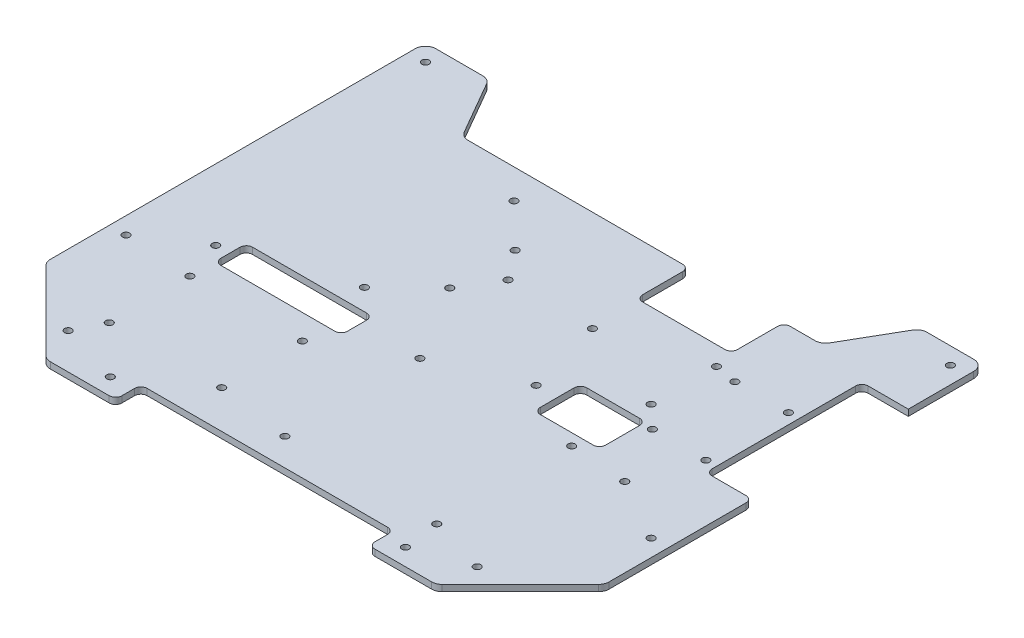
SolidWorks part; units mm, degrees
material "Acier non allié"
ref_plane "Front" through (0, 0, 0) normal (0, 0, 1) x (1, 0, 0)
ref_plane "Top" through (0, 0, 0) normal (0, 1, 0) x (1, 0, 0)
ref_plane "Right" through (0, 0, 0) normal (1, 0, 0) x (0, 0, -1)
sketch "Esquisse1" plane through (0, 0, 0) normal (0, 1, 0) x (1, 0, 0)
  line L0 (0, 0) -> (0, 190) construction
  line L1 (-92.5, 0) -> (92.5, 0)
  line L2 (92.5, 0) -> (132.5, 40)
  line L3 (132.5, 40) -> (132.5, 220)
  line L4 (132.5, 220) -> (102.5, 220)
  line L5 (102.5, 220) -> (85.1795, 190)
  line L6 (85.1795, 190) -> (-85.1795, 190)
  line L7 (-102.5, 220) -> (-85.1795, 190)
  line L8 (-132.5, 220) -> (-102.5, 220)
  line L9 (-132.5, 40) -> (-132.5, 220)
  line L10 (-92.5, 0) -> (-132.5, 40)
  dimension "D1" = 132.5
  dimension "D2" = 220
  dimension "D3" = 60
  dimension "D4" = 30
  dimension "D5" = 40
  dimension "D6" = 40
  dimension "D7" = 30
extrude "Boss.-Extru.1" add sketch "Esquisse1" along normal blind 3
fillet "Congé1" radius 5 10 edges at (92.5, 1.5, 0) (132.5, 1.5, -40) (132.5, 1.5, -220) (102.5, 1.5, -220) (85.1795, 1.5, -190) (-85.1795, 1.5, -190) (-102.5, 1.5, -220) (-132.5, 1.5, -220) (-92.5, 1.5, 0) (-132.5, 1.5, -40)
sketch "Esquisse2" plane through (0, 3, 0) normal (0, 1, 0) x (1, 0, 0)
  line L0 (0, 0) -> (0, 294.1173) construction
  line L2 (-90.4289, 0) -> (90.4289, 0) construction
  circle A0 centre (70, 8) radius 1
  circle A1 centre (124.5, 70) radius 1
  circle A2 centre (124.5, 212) radius 1
  circle A3 centre (-124.5, 212) radius 1
  circle A4 centre (-124.5, 70) radius 1
  circle A5 centre (-70, 8) radius 1
  dimension "D2" = 2
  dimension "D6" = 2
  dimension "D9" = 2
  dimension "D1" = 70
  dimension "D3" = 8
  dimension "D4" = 124.5
  dimension "D5" = 70
  dimension "D7" = 124.5
  dimension "D8" = 212
extrude "Enlèv. mat.-Extru.1" cut sketch "Esquisse2" against normal blind 3
hole_wizard "Dégagement M31" positions "Esquisse3" profile "Esquisse4" hole size "M3" standard "ISO" end condition through all
sketch "Esquisse3" plane through (0, 3, 0) normal (0, 1, 0) x (1, 0, 0)
  point P0 (70, 8)
  point P3 (-70, 8)
  point P6 (-124.5, 70)
  point P9 (-124.5, 212)
  point P12 (124.5, 212)
  point P15 (124.5, 70)
sketch "Esquisse4" plane through (70, 3, -8) normal (1, 0, 0) x (0, 0, 1)
  line L0 (0, 0) -> (0, 3)
  line L1 (0, 3) -> (1.7, 3)
  line L2 (1.7, 3) -> (1.7, 0)
  line L5 (1.7, 0) -> (0, 0)
  line L11 (0, -6.35) -> (0, 107.95) construction
  dimension "Diamètre du perçage jusqu'au prochain" = 3.4
  dimension "Profondeur du perçage jusqu'au prochain" = 3
sketch "Esquisse5" plane through (0, 3, 0) normal (0, 1, 0) x (1, 0, 0)
  line L0 (82.2927, 190) -> (-82.2927, 190) construction
  line L1 (67.5, 190) -> (22.5, 190)
  line L2 (67.5, 190) -> (67.5, 165)
  line L3 (67.5, 165) -> (22.5, 165)
  line L4 (22.5, 190) -> (22.5, 165)
  line L5 (132.5, 42.0711) -> (132.5, 215) construction
  line L6 (132.5, 184) -> (110.5, 184)
  line L7 (132.5, 184) -> (132.5, 110)
  line L8 (132.5, 110) -> (110.5, 110)
  line L9 (110.5, 184) -> (110.5, 110)
  line L10 (127.5, 220) -> (105.3868, 220) construction
  dimension "D1" = 25
  dimension "D2" = 65
  dimension "D3" = 110
  dimension "D4" = 36
  dimension "D5" = 110
  dimension "D6" = 22
extrude "Enlèv. mat.-Extru.2" cut sketch "Esquisse5" against normal through all
fillet "Congé2" radius 3 7 edges at (132.5, 1.5, -110) (110.5, 1.5, -110) (110.5, 1.5, -184) (67.5, 1.5, -190) (67.5, 1.5, -165) (22.5, 1.5, -165) (22.5, 1.5, -190)
sketch "Esquisse6" plane through (0, 3, 0) normal (0, 1, 0) x (1, 0, 0)
  line L0 (110.5, 140.5) -> (-167.6757, 140.5) construction
  line L1 (110.5, 181) -> (110.5, 113) construction
  line L2 (-90.4289, 0) -> (90.4289, 0) construction
  line L3 (110.5, 181) -> (110.5, 113) construction
  circle A0 centre (69.5, 156) radius 1
  circle A1 centre (-26, 156) radius 1
  circle A2 centre (-46.5, 176) radius 1
  circle A3 centre (69.5, 125) radius 1
  circle A4 centre (-26, 125) radius 1
  circle A5 centre (-46.5, 105) radius 1
  dimension "D4" = 2
  dimension "D6" = 2
  dimension "D10" = 2
  dimension "D1" = 140.5
  dimension "D2" = 41
  dimension "D3" = 15.5
  dimension "D5" = 136.5
  dimension "D7" = 15.5
  dimension "D8" = 35.5
  dimension "D9" = 157
extrude "Enlèv. mat.-Extru.3" cut sketch "Esquisse6" against normal through all
hole_wizard "Dégagement M32" positions "Esquisse7" profile "Esquisse8" hole size "M3" standard "ISO"
sketch "Esquisse7" plane through (0, 3, 0) normal (0, 1, 0) x (1, 0, 0)
  point P0 (-46.5, 105)
  point P3 (-26, 125)
  point P6 (-26, 156)
  point P9 (-46.5, 176)
  point P12 (69.5, 156)
  point P15 (69.5, 125)
sketch "Esquisse8" plane through (-46.5, 3, -105) normal (1, 0, 0) x (0, 0, 1)
  line L0 (0, 0) -> (0, 11.0215)
  line L1 (0, 11.0215) -> (1.7, 10)
  line L2 (1.7, 10) -> (1.7, 0)
  line L5 (1.7, 0) -> (0, 0)
  line L10 (0, 11.0215) -> (-1.7, 10) construction
  line L11 (0, -6.35) -> (0, 107.95) construction
  dimension "Diamètre du perçage" = 3.4
  dimension "Profondeur du perçage" = 10
  dimension "Angle de pointe" = 118
sketch "Esquisse9" plane through (0, 3, 0) normal (0, 1, 0) x (1, 0, 0)
  line L0 (132.5, 42.0711) -> (132.5, 107) construction
  line L1 (-90.4289, 0) -> (90.4289, 0) construction
  line L2 (-132.5, 215) -> (-132.5, 42.0711) construction
  line L3 (-39.16, 30) -> (-92.5, 30) construction
  line L4 (-39.16, 30) -> (-39.16, 68.24) construction
  line L5 (-39.16, 68.24) -> (-92.5, 68.24) construction
  line L6 (-92.5, 30) -> (-92.5, 68.24) construction
  line L7 (-4.16, 25) -> (-4.16, 89) construction
  line L8 (25.5, 165) -> (64.5, 165) construction
  line L9 (24.5, 142.1606) -> (-15.5, 142.1606) construction
  line L10 (110.5, 181) -> (110.5, 113) construction
  line L11 (113.5, 110) -> (129.5, 110) construction
  circle A0 centre (105.5, 115) radius 1
  circle A3 centre (105.5, 154.12) radius 1
  circle A6 centre (-92.5, 68.24) radius 1
  circle A7 centre (-39.16, 68.24) radius 1
  circle A8 centre (-39.16, 30) radius 1
  circle A9 centre (-92.5, 30) radius 1
  circle A10 centre (-4.16, 89) radius 1
  circle A11 centre (67.84, 89) radius 1
  circle A12 centre (-4.16, 25) radius 1
  circle A13 centre (67.84, 25) radius 1
  circle A14 centre (-15.5, 142.1606) radius 1
  circle A15 centre (24.5, 142.1606) radius 1
  circle A16 centre (34.5, 105.5) radius 1
  circle A17 centre (80.1, 115) radius 1
  circle A18 centre (80.1, 154.12) radius 1
  dimension "D2" = 2
  dimension "D4" = 2
  dimension "D17" = 2
  dimension "D18" = 2
  dimension "D19" = 2
  dimension "D20" = 2
  dimension "D21" = 2
  dimension "D22" = 2
  dimension "D23" = 2
  dimension "D24" = 2
  dimension "D32" = 2
  dimension "D33" = 2
  dimension "D34" = 2
  dimension "D11" = 2
  dimension "D12" = 2
  dimension "D5" = 27
  dimension "25" = 27
  dimension "D10" = 39.12
  dimension "D13" = 38.24
  dimension "D14" = 53.34
  dimension "D15" = 30
  dimension "D16" = 40
  dimension "D25" = 72
  dimension "D26" = 72
  dimension "D27" = 64
  dimension "D28" = 64
  dimension "D29" = 35
  dimension "D30" = 25
  dimension "D31" = 25
  dimension "D36" = 38
  dimension "D37" = 40
  dimension "D39" = 10
  dimension "D7" = 5
  dimension "D8" = 25.4
  dimension "D9" = 25.4
  dimension "D40" = 39.12
  dimension "D35" = 59.5
  dimension "D38" = 76
extrude "Enlèv. mat.-Extru.4" cut sketch "Esquisse9" against normal through all
hole_wizard "Dégagement M33" positions "Esquisse10" profile "Esquisse11" hole size "M3" standard "ISO"
sketch "Esquisse10" plane through (0, 3, 0) normal (0, 1, 0) x (1, 0, 0)
  point P3 (105.5, 115)
  point P9 (105.5, 154.12)
  point P14 (80.1, 154.12)
  point P17 (80.1, 115)
sketch "Esquisse11" plane through (105.5, 3, -115) normal (1, 0, 0) x (0, 0, 1)
  line L0 (0, 0) -> (0, 11.0215)
  line L1 (0, 11.0215) -> (1.7, 10)
  line L2 (1.7, 10) -> (1.7, 0)
  line L5 (1.7, 0) -> (0, 0)
  line L10 (0, 11.0215) -> (-1.7, 10) construction
  line L11 (0, -6.35) -> (0, 107.95) construction
  dimension "Diamètre du perçage" = 3.4
  dimension "Profondeur du perçage" = 10
  dimension "Angle de pointe" = 118
sketch "Esquisse12" plane through (0, 3, 0) normal (0, 1, 0) x (1, 0, 0)
  line L2 (-90.4289, 0) -> (90.4289, 0) construction
  line L3 (95, 17) -> (-99, 17) construction
  line L4 (95, 17) -> (95, 87) construction
  line L5 (95, 87) -> (-99, 87) construction
  line L6 (-99, 17) -> (-99, 87) construction
  line L7 (132.5, 42.0711) -> (132.5, 107) construction
  circle A4 centre (-99, 87) radius 1
  circle A5 centre (95, 87) radius 1
  circle A6 centre (95, 17) radius 1
  circle A7 centre (-99, 17) radius 1
  point P6 (95, 52)
  dimension "D5" = 2
  dimension "D6" = 2
  dimension "D7" = 2
  dimension "D8" = 2
  dimension "D1" = 70
  dimension "D2" = 194
  dimension "D3" = 17
  dimension "D4" = 37.5
extrude "Enlèv. mat.-Extru.5" cut sketch "Esquisse12" against normal through all and the other way through all
hole_wizard "Dégagement M34" positions "Esquisse13" profile "Esquisse14" hole size "M3" standard "ISO"
sketch "Esquisse13" plane through (0, 3, 0) normal (0, 1, 0) x (1, 0, 0)
  point P3 (-92.5, 68.24)
  point P6 (-92.5, 30)
  point P9 (-39.16, 30)
  point P12 (-39.16, 68.24)
  point P16 (-4.16, 25)
  point P19 (67.84, 25)
  point P22 (-4.16, 89)
  point P25 (67.84, 89)
  point P29 (34.5, 105.5)
  point P32 (24.5, 142.1606)
  point P35 (-15.5, 142.1606)
sketch "Esquisse14" plane through (-92.5, 3, -68.24) normal (1, 0, 0) x (0, 0, 1)
  line L0 (0, 0) -> (0, 11.0215)
  line L1 (0, 11.0215) -> (1.7, 10)
  line L2 (1.7, 10) -> (1.7, 0)
  line L5 (1.7, 0) -> (0, 0)
  line L10 (0, 11.0215) -> (-1.7, 10) construction
  line L11 (0, -6.35) -> (0, 107.95) construction
  dimension "Diamètre du perçage" = 3.4
  dimension "Profondeur du perçage" = 10
  dimension "Angle de pointe" = 118
hole_wizard "Dégagement M35" positions "Esquisse15" profile "Esquisse16" hole size "M3" standard "ISO"
sketch "Esquisse15" plane through (0, 3, 0) normal (0, 1, 0) x (1, 0, 0)
  point P0 (-99, 17)
  point P3 (-99, 87)
  point P6 (95, 87)
  point P9 (95, 17)
sketch "Esquisse16" plane through (-99, 3, -17) normal (1, 0, 0) x (0, 0, 1)
  line L0 (0, 0) -> (0, 11.0215)
  line L1 (0, 11.0215) -> (1.7, 10)
  line L2 (1.7, 10) -> (1.7, 0)
  line L5 (1.7, 0) -> (0, 0)
  line L10 (0, 11.0215) -> (-1.7, 10) construction
  line L11 (0, -6.35) -> (0, 107.95) construction
  dimension "Diamètre du perçage" = 3.4
  dimension "Profondeur du perçage" = 10
  dimension "Angle de pointe" = 118
sketch "Esquisse17" plane through (0, 3, 0) normal (0, 1, 0) x (1, 0, 0)
  line L0 (-90.4289, 0) -> (90.4289, 0) construction
  line L1 (-92.5, 95) -> (-32.5, 95)
  line L2 (-92.5, 95) -> (-92.5, 80)
  line L3 (-92.5, 80) -> (-32.5, 80)
  line L4 (-32.5, 95) -> (-32.5, 80)
  line L5 (-132.5, 215) -> (-132.5, 42.0711) construction
  line L6 (132.5, 42.0711) -> (132.5, 107) construction
  line L7 (44.5, 116.5) -> (75.5, 116.5)
  line L8 (44.5, 116.5) -> (44.5, 94.5)
  line L9 (44.5, 94.5) -> (75.5, 94.5)
  line L10 (75.5, 116.5) -> (75.5, 94.5)
  line L11 (82.2927, 190) -> (70.5, 190) construction
  line L13 (-59.5, 12) -> (60.5, 12)
  line L14 (-59.5, 12) -> (-59.5, 0)
  line L15 (-59.5, 0) -> (60.5, 0)
  line L16 (60.5, 12) -> (60.5, 0)
  dimension "D1" = 60
  dimension "D2" = 15
  dimension "D3" = 80
  dimension "D4" = 40
  dimension "D5" = 31
  dimension "D6" = 22
  dimension "D7" = 57
  dimension "D8" = 73.5
  dimension "D9" = 12
  dimension "D11" = 120
  dimension "D12" = 72
extrude "Enlèv. mat.-Extru.6" cut sketch "Esquisse17" against normal up to surface (3 mm away) up to face at (-99, 0, -15.3)
fillet "Congé3" radius 3 12 edges at (60.5, 1.5, 0) (60.5, 1.5, -12) (-59.5, 1.5, -12) (-59.5, 1.5, 0) (44.5, 1.5, -116.5) (75.5, 1.5, -116.5) (75.5, 1.5, -94.5) (44.5, 1.5, -94.5) (-92.5, 1.5, -80) (-32.5, 1.5, -80) (-32.5, 1.5, -95) (-92.5, 1.5, -95)
equation "\"WIDTH\"= 300mm'Total width of the robot"
equation "\"LENGTH\"= 220mm'Total length of the robot"
equation "\"CUT_DEPTH\"= 45mm'Depth of the cut on the edges of the plate"
equation "\"Plate_th\"= 3mm'Thickness of the plate"
equation "\"D1\"= \"Plate_th\""
equation "\"D5@Esquisse9\"=\"25@Esquisse9\""
